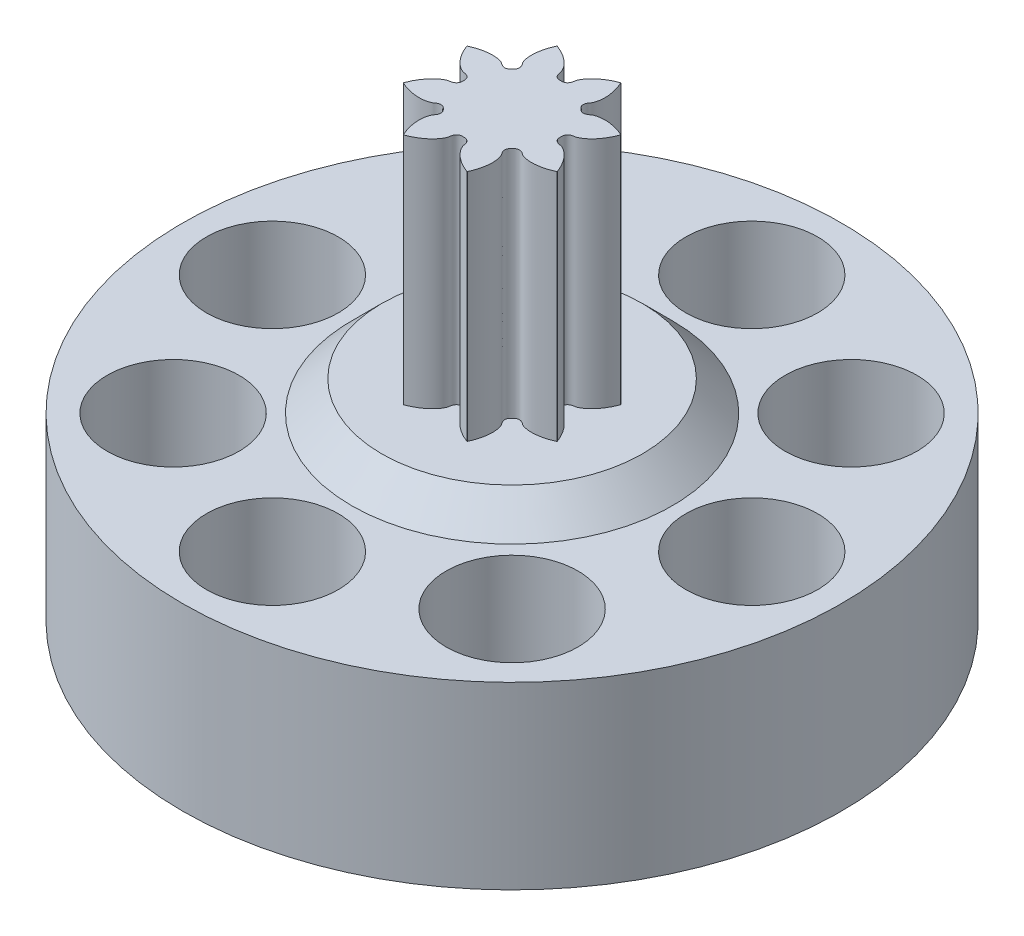
SolidWorks part; units mm, degrees
other "Markup1"
sketch "Sketch16" plane through (11, -3, 11) normal (0.0109, -0.9996, 0.0259) x (-0.0225, -0.0261, -0.9994)
ref_plane "Front Plane" through (0, 0, 0) normal (0, 0, 1) x (1, 0, 0)
ref_plane "Top Plane" through (0, 0, 0) normal (0, 1, 0) x (1, 0, 0)
ref_plane "Right Plane" through (0, 0, 0) normal (1, 0, 0) x (0, 0, -1)
sketch "Sketch1" plane through (0, 0, 0) normal (0, 1, 0) x (1, 0, 0)
  circle A0 centre (0, 0) radius 11
  dimension "D1" = 22
extrude "Boss-Extrude1" add sketch "Sketch1" along normal mid plane 6
sketch "Sketch2" plane through (0, 3, 0) normal (0, 1, 0) x (1, 0, 0)
  circle A0 centre (0, 8) radius 1
  circle A1 centre (-5.6569, 5.6569) radius 1
  circle A2 centre (5.6569, 5.6569) radius 1
  circle A3 centre (-5.6569, -5.6569) radius 1
  circle A4 centre (5.6569, -5.6569) radius 1
  circle A5 centre (-8, 0) radius 1
  circle A6 centre (0, -8) radius 1
  circle A7 centre (8, 0) radius 1
  circle A8 centre (0, 0) radius 4
  circle A9 centre (0, 0) radius 11
sketch "Sketch5" plane through (0, 3, 0) normal (0, 1, 0) x (1, 0, 0)
  line L0 (2.5656, 1.0576) -> (2.562, 1.0663)
  line L1 (1.0663, 2.562) -> (1.0576, 2.5656)
  line L2 (-1.0576, 2.5656) -> (-1.0663, 2.562)
  line L3 (-2.562, 1.0663) -> (-2.5656, 1.0576)
  line L4 (-2.5656, -1.0576) -> (-2.562, -1.0663)
  line L5 (-1.0663, -2.562) -> (-1.0576, -2.5656)
  line L6 (1.0576, -2.5656) -> (1.0663, -2.562)
  line L7 (2.562, -1.0663) -> (2.5656, -1.0576)
  circle A1 centre (0, 0) radius 2.8
  spline S0 degree 3 poles (2.5656, 1.0576) (2.5467, 1.0063) (2.5127, 0.9243) (2.4586, 0.8162) (2.4108, 0.7326) (2.3616, 0.6567) (2.3117, 0.5883) (2.2618, 0.5274) (2.2125, 0.4736) (2.1645, 0.4267) (2.1184, 0.3865) (2.0746, 0.3524) (2.0339, 0.3241) (1.9966, 0.3012) (1.9632, 0.2831) (1.9342, 0.2695) (1.9099, 0.2596) (1.8905, 0.253) (1.8694, 0.2467) (1.8487, 0.2452) (1.828, 0.2423) (1.8074, 0.2387) (1.7821, 0.2325) (1.7521, 0.2221) (1.7278, 0.2103) (1.7086, 0.1983) (1.6939, 0.1875) (1.6793, 0.1746) (1.665, 0.1592) (1.6515, 0.1408) (1.6395, 0.1191) (1.6301, 0.0941) (1.6246, 0.0677) (1.6231, 0.036) (1.6249, 0) (1.6231, -0.036) (1.6246, -0.0677) (1.6301, -0.0941) (1.6395, -0.1191) (1.6515, -0.1408) (1.665, -0.1592) (1.6793, -0.1746) (1.6982, -0.1913) (1.7224, -0.2076) (1.7521, -0.2221) (1.7821, -0.2325) (1.8074, -0.2387) (1.828, -0.2423) (1.8487, -0.2452) (1.8694, -0.2467) (1.8905, -0.253) (1.9099, -0.2596) (1.9342, -0.2695) (1.9632, -0.2831) (1.9966, -0.3012) (2.0339, -0.3241) (2.0746, -0.3524) (2.1184, -0.3865) (2.1645, -0.4267) (2.2125, -0.4736) (2.2618, -0.5274) (2.3117, -0.5883) (2.3616, -0.6567) (2.4108, -0.7326) (2.4586, -0.8162) (2.5127, -0.9243) (2.5467, -1.0063) (2.5656, -1.0576) knots 0.018496 0.018496 0.018496 0.018496 0.071158 0.103928 0.134826 0.16385 0.191003 0.216283 0.23969 0.261224 0.280886 0.298676 0.314593 0.328637 0.340809 0.351108 0.359535 0.366089 0.37077 0.380767 0.385886 0.390938 0.400931 0.410975 0.421412 0.426928 0.432746 0.438959 0.445665 0.452957 0.460893 0.469469 0.478579 0.486756 0.5 0.513244 0.521421 0.530531 0.539107 0.547043 0.554335 0.561041 0.567254 0.578588 0.589025 0.599069 0.609062 0.614114 0.619233 0.62923 0.633911 0.640465 0.648892 0.659191 0.671363 0.685407 0.701324 0.719114 0.738776 0.76031 0.783717 0.808997 0.83615 0.865174 0.896072 0.928842 0.981504 0.981504 0.981504 0.981504
  spline S1 degree 3 poles (1.0663, 2.562) (1.0892, 2.5123) (1.1232, 2.4303) (1.1614, 2.3156) (1.1867, 2.2227) (1.2056, 2.1343) (1.2186, 2.0507) (1.2264, 1.9723) (1.2296, 1.8994) (1.2288, 1.8323) (1.2246, 1.7712) (1.2178, 1.7162) (1.209, 1.6673) (1.1988, 1.6248) (1.188, 1.5884) (1.1771, 1.5582) (1.1669, 1.534) (1.1579, 1.5157) (1.1474, 1.4963) (1.1339, 1.4806) (1.1212, 1.464) (1.1092, 1.4468) (1.0957, 1.4245) (1.0819, 1.396) (1.0731, 1.3704) (1.0679, 1.3484) (1.0652, 1.3304) (1.0639, 1.3109) (1.0647, 1.2899) (1.0682, 1.2673) (1.0751, 1.2435) (1.0861, 1.2192) (1.1009, 1.1966) (1.1223, 1.1732) (1.149, 1.149) (1.1732, 1.1223) (1.1966, 1.1009) (1.2192, 1.0861) (1.2435, 1.0751) (1.2673, 1.0682) (1.2899, 1.0647) (1.3109, 1.0639) (1.3361, 1.0655) (1.3647, 1.0711) (1.396, 1.0819) (1.4245, 1.0957) (1.4468, 1.1092) (1.464, 1.1212) (1.4806, 1.1339) (1.4963, 1.1474) (1.5157, 1.1579) (1.534, 1.1669) (1.5582, 1.1771) (1.5884, 1.188) (1.6248, 1.1988) (1.6673, 1.209) (1.7162, 1.2178) (1.7712, 1.2246) (1.8323, 1.2288) (1.8994, 1.2296) (1.9723, 1.2264) (2.0507, 1.2186) (2.1343, 1.2056) (2.2227, 1.1867) (2.3156, 1.1614) (2.4303, 1.1232) (2.5123, 1.0892) (2.562, 1.0663) knots 0.018496 0.018496 0.018496 0.018496 0.071158 0.103928 0.134826 0.16385 0.191003 0.216283 0.23969 0.261224 0.280886 0.298676 0.314593 0.328637 0.340809 0.351108 0.359535 0.366089 0.37077 0.380767 0.385886 0.390938 0.400931 0.410975 0.421412 0.426928 0.432746 0.438959 0.445665 0.452957 0.460893 0.469469 0.478579 0.486756 0.5 0.513244 0.521421 0.530531 0.539107 0.547043 0.554335 0.561041 0.567254 0.578588 0.589025 0.599069 0.609062 0.614114 0.619233 0.62923 0.633911 0.640465 0.648892 0.659191 0.671363 0.685407 0.701324 0.719114 0.738776 0.76031 0.783717 0.808997 0.83615 0.865174 0.896072 0.928842 0.981504 0.981504 0.981504 0.981504
  spline S2 degree 3 poles (-1.0576, 2.5656) (-1.0063, 2.5467) (-0.9243, 2.5127) (-0.8162, 2.4586) (-0.7326, 2.4108) (-0.6567, 2.3616) (-0.5883, 2.3117) (-0.5274, 2.2618) (-0.4736, 2.2125) (-0.4267, 2.1645) (-0.3865, 2.1184) (-0.3524, 2.0746) (-0.3241, 2.0339) (-0.3012, 1.9966) (-0.2831, 1.9632) (-0.2695, 1.9342) (-0.2596, 1.9099) (-0.253, 1.8905) (-0.2467, 1.8694) (-0.2452, 1.8487) (-0.2423, 1.828) (-0.2387, 1.8074) (-0.2325, 1.7821) (-0.2221, 1.7521) (-0.2103, 1.7278) (-0.1983, 1.7086) (-0.1875, 1.6939) (-0.1746, 1.6793) (-0.1592, 1.665) (-0.1408, 1.6515) (-0.1191, 1.6395) (-0.0941, 1.6301) (-0.0677, 1.6246) (-0.036, 1.6231) (0, 1.6249) (0.036, 1.6231) (0.0677, 1.6246) (0.0941, 1.6301) (0.1191, 1.6395) (0.1408, 1.6515) (0.1592, 1.665) (0.1746, 1.6793) (0.1913, 1.6982) (0.2076, 1.7224) (0.2221, 1.7521) (0.2325, 1.7821) (0.2387, 1.8074) (0.2423, 1.828) (0.2452, 1.8487) (0.2467, 1.8694) (0.253, 1.8905) (0.2596, 1.9099) (0.2695, 1.9342) (0.2831, 1.9632) (0.3012, 1.9966) (0.3241, 2.0339) (0.3524, 2.0746) (0.3865, 2.1184) (0.4267, 2.1645) (0.4736, 2.2125) (0.5274, 2.2618) (0.5883, 2.3117) (0.6567, 2.3616) (0.7326, 2.4108) (0.8162, 2.4586) (0.9243, 2.5127) (1.0063, 2.5467) (1.0576, 2.5656) knots 0.018496 0.018496 0.018496 0.018496 0.071158 0.103928 0.134826 0.16385 0.191003 0.216283 0.23969 0.261224 0.280886 0.298676 0.314593 0.328637 0.340809 0.351108 0.359535 0.366089 0.37077 0.380767 0.385886 0.390938 0.400931 0.410975 0.421412 0.426928 0.432746 0.438959 0.445665 0.452957 0.460893 0.469469 0.478579 0.486756 0.5 0.513244 0.521421 0.530531 0.539107 0.547043 0.554335 0.561041 0.567254 0.578588 0.589025 0.599069 0.609062 0.614114 0.619233 0.62923 0.633911 0.640465 0.648892 0.659191 0.671363 0.685407 0.701324 0.719114 0.738776 0.76031 0.783717 0.808997 0.83615 0.865174 0.896072 0.928842 0.981504 0.981504 0.981504 0.981504
  spline S3 degree 3 poles (-2.562, 1.0663) (-2.5123, 1.0892) (-2.4303, 1.1232) (-2.3156, 1.1614) (-2.2227, 1.1867) (-2.1343, 1.2056) (-2.0507, 1.2186) (-1.9723, 1.2264) (-1.8994, 1.2296) (-1.8323, 1.2288) (-1.7712, 1.2246) (-1.7162, 1.2178) (-1.6673, 1.209) (-1.6248, 1.1988) (-1.5884, 1.188) (-1.5582, 1.1771) (-1.534, 1.1669) (-1.5157, 1.1579) (-1.4963, 1.1474) (-1.4806, 1.1339) (-1.464, 1.1212) (-1.4468, 1.1092) (-1.4245, 1.0957) (-1.396, 1.0819) (-1.3704, 1.0731) (-1.3484, 1.0679) (-1.3304, 1.0652) (-1.3109, 1.0639) (-1.2899, 1.0647) (-1.2673, 1.0682) (-1.2435, 1.0751) (-1.2192, 1.0861) (-1.1966, 1.1009) (-1.1732, 1.1223) (-1.149, 1.149) (-1.1223, 1.1732) (-1.1009, 1.1966) (-1.0861, 1.2192) (-1.0751, 1.2435) (-1.0682, 1.2673) (-1.0647, 1.2899) (-1.0639, 1.3109) (-1.0655, 1.3361) (-1.0711, 1.3647) (-1.0819, 1.396) (-1.0957, 1.4245) (-1.1092, 1.4468) (-1.1212, 1.464) (-1.1339, 1.4806) (-1.1474, 1.4963) (-1.1579, 1.5157) (-1.1669, 1.534) (-1.1771, 1.5582) (-1.188, 1.5884) (-1.1988, 1.6248) (-1.209, 1.6673) (-1.2178, 1.7162) (-1.2246, 1.7712) (-1.2288, 1.8323) (-1.2296, 1.8994) (-1.2264, 1.9723) (-1.2186, 2.0507) (-1.2056, 2.1343) (-1.1867, 2.2227) (-1.1614, 2.3156) (-1.1232, 2.4303) (-1.0892, 2.5123) (-1.0663, 2.562) knots 0.018496 0.018496 0.018496 0.018496 0.071158 0.103928 0.134826 0.16385 0.191003 0.216283 0.23969 0.261224 0.280886 0.298676 0.314593 0.328637 0.340809 0.351108 0.359535 0.366089 0.37077 0.380767 0.385886 0.390938 0.400931 0.410975 0.421412 0.426928 0.432746 0.438959 0.445665 0.452957 0.460893 0.469469 0.478579 0.486756 0.5 0.513244 0.521421 0.530531 0.539107 0.547043 0.554335 0.561041 0.567254 0.578588 0.589025 0.599069 0.609062 0.614114 0.619233 0.62923 0.633911 0.640465 0.648892 0.659191 0.671363 0.685407 0.701324 0.719114 0.738776 0.76031 0.783717 0.808997 0.83615 0.865174 0.896072 0.928842 0.981504 0.981504 0.981504 0.981504
  spline S4 degree 3 poles (-2.5656, -1.0576) (-2.5467, -1.0063) (-2.5127, -0.9243) (-2.4586, -0.8162) (-2.4108, -0.7326) (-2.3616, -0.6567) (-2.3117, -0.5883) (-2.2618, -0.5274) (-2.2125, -0.4736) (-2.1645, -0.4267) (-2.1184, -0.3865) (-2.0746, -0.3524) (-2.0339, -0.3241) (-1.9966, -0.3012) (-1.9632, -0.2831) (-1.9342, -0.2695) (-1.9099, -0.2596) (-1.8905, -0.253) (-1.8694, -0.2467) (-1.8487, -0.2452) (-1.828, -0.2423) (-1.8074, -0.2387) (-1.7821, -0.2325) (-1.7521, -0.2221) (-1.7278, -0.2103) (-1.7086, -0.1983) (-1.6939, -0.1875) (-1.6793, -0.1746) (-1.665, -0.1592) (-1.6515, -0.1408) (-1.6395, -0.1191) (-1.6301, -0.0941) (-1.6246, -0.0677) (-1.6231, -0.036) (-1.6249, 0) (-1.6231, 0.036) (-1.6246, 0.0677) (-1.6301, 0.0941) (-1.6395, 0.1191) (-1.6515, 0.1408) (-1.665, 0.1592) (-1.6793, 0.1746) (-1.6982, 0.1913) (-1.7224, 0.2076) (-1.7521, 0.2221) (-1.7821, 0.2325) (-1.8074, 0.2387) (-1.828, 0.2423) (-1.8487, 0.2452) (-1.8694, 0.2467) (-1.8905, 0.253) (-1.9099, 0.2596) (-1.9342, 0.2695) (-1.9632, 0.2831) (-1.9966, 0.3012) (-2.0339, 0.3241) (-2.0746, 0.3524) (-2.1184, 0.3865) (-2.1645, 0.4267) (-2.2125, 0.4736) (-2.2618, 0.5274) (-2.3117, 0.5883) (-2.3616, 0.6567) (-2.4108, 0.7326) (-2.4586, 0.8162) (-2.5127, 0.9243) (-2.5467, 1.0063) (-2.5656, 1.0576) knots 0.018496 0.018496 0.018496 0.018496 0.071158 0.103928 0.134826 0.16385 0.191003 0.216283 0.23969 0.261224 0.280886 0.298676 0.314593 0.328637 0.340809 0.351108 0.359535 0.366089 0.37077 0.380767 0.385886 0.390938 0.400931 0.410975 0.421412 0.426928 0.432746 0.438959 0.445665 0.452957 0.460893 0.469469 0.478579 0.486756 0.5 0.513244 0.521421 0.530531 0.539107 0.547043 0.554335 0.561041 0.567254 0.578588 0.589025 0.599069 0.609062 0.614114 0.619233 0.62923 0.633911 0.640465 0.648892 0.659191 0.671363 0.685407 0.701324 0.719114 0.738776 0.76031 0.783717 0.808997 0.83615 0.865174 0.896072 0.928842 0.981504 0.981504 0.981504 0.981504
  spline S5 degree 3 poles (-1.0663, -2.562) (-1.0892, -2.5123) (-1.1232, -2.4303) (-1.1614, -2.3156) (-1.1867, -2.2227) (-1.2056, -2.1343) (-1.2186, -2.0507) (-1.2264, -1.9723) (-1.2296, -1.8994) (-1.2288, -1.8323) (-1.2246, -1.7712) (-1.2178, -1.7162) (-1.209, -1.6673) (-1.1988, -1.6248) (-1.188, -1.5884) (-1.1771, -1.5582) (-1.1669, -1.534) (-1.1579, -1.5157) (-1.1474, -1.4963) (-1.1339, -1.4806) (-1.1212, -1.464) (-1.1092, -1.4468) (-1.0957, -1.4245) (-1.0819, -1.396) (-1.0731, -1.3704) (-1.0679, -1.3484) (-1.0652, -1.3304) (-1.0639, -1.3109) (-1.0647, -1.2899) (-1.0682, -1.2673) (-1.0751, -1.2435) (-1.0861, -1.2192) (-1.1009, -1.1966) (-1.1223, -1.1732) (-1.149, -1.149) (-1.1732, -1.1223) (-1.1966, -1.1009) (-1.2192, -1.0861) (-1.2435, -1.0751) (-1.2673, -1.0682) (-1.2899, -1.0647) (-1.3109, -1.0639) (-1.3361, -1.0655) (-1.3647, -1.0711) (-1.396, -1.0819) (-1.4245, -1.0957) (-1.4468, -1.1092) (-1.464, -1.1212) (-1.4806, -1.1339) (-1.4963, -1.1474) (-1.5157, -1.1579) (-1.534, -1.1669) (-1.5582, -1.1771) (-1.5884, -1.188) (-1.6248, -1.1988) (-1.6673, -1.209) (-1.7162, -1.2178) (-1.7712, -1.2246) (-1.8323, -1.2288) (-1.8994, -1.2296) (-1.9723, -1.2264) (-2.0507, -1.2186) (-2.1343, -1.2056) (-2.2227, -1.1867) (-2.3156, -1.1614) (-2.4303, -1.1232) (-2.5123, -1.0892) (-2.562, -1.0663) knots 0.018496 0.018496 0.018496 0.018496 0.071158 0.103928 0.134826 0.16385 0.191003 0.216283 0.23969 0.261224 0.280886 0.298676 0.314593 0.328637 0.340809 0.351108 0.359535 0.366089 0.37077 0.380767 0.385886 0.390938 0.400931 0.410975 0.421412 0.426928 0.432746 0.438959 0.445665 0.452957 0.460893 0.469469 0.478579 0.486756 0.5 0.513244 0.521421 0.530531 0.539107 0.547043 0.554335 0.561041 0.567254 0.578588 0.589025 0.599069 0.609062 0.614114 0.619233 0.62923 0.633911 0.640465 0.648892 0.659191 0.671363 0.685407 0.701324 0.719114 0.738776 0.76031 0.783717 0.808997 0.83615 0.865174 0.896072 0.928842 0.981504 0.981504 0.981504 0.981504
  spline S6 degree 3 poles (1.0576, -2.5656) (1.0063, -2.5467) (0.9243, -2.5127) (0.8162, -2.4586) (0.7326, -2.4108) (0.6567, -2.3616) (0.5883, -2.3117) (0.5274, -2.2618) (0.4736, -2.2125) (0.4267, -2.1645) (0.3865, -2.1184) (0.3524, -2.0746) (0.3241, -2.0339) (0.3012, -1.9966) (0.2831, -1.9632) (0.2695, -1.9342) (0.2596, -1.9099) (0.253, -1.8905) (0.2467, -1.8694) (0.2452, -1.8487) (0.2423, -1.828) (0.2387, -1.8074) (0.2325, -1.7821) (0.2221, -1.7521) (0.2103, -1.7278) (0.1983, -1.7086) (0.1875, -1.6939) (0.1746, -1.6793) (0.1592, -1.665) (0.1408, -1.6515) (0.1191, -1.6395) (0.0941, -1.6301) (0.0677, -1.6246) (0.036, -1.6231) (0, -1.6249) (-0.036, -1.6231) (-0.0677, -1.6246) (-0.0941, -1.6301) (-0.1191, -1.6395) (-0.1408, -1.6515) (-0.1592, -1.665) (-0.1746, -1.6793) (-0.1913, -1.6982) (-0.2076, -1.7224) (-0.2221, -1.7521) (-0.2325, -1.7821) (-0.2387, -1.8074) (-0.2423, -1.828) (-0.2452, -1.8487) (-0.2467, -1.8694) (-0.253, -1.8905) (-0.2596, -1.9099) (-0.2695, -1.9342) (-0.2831, -1.9632) (-0.3012, -1.9966) (-0.3241, -2.0339) (-0.3524, -2.0746) (-0.3865, -2.1184) (-0.4267, -2.1645) (-0.4736, -2.2125) (-0.5274, -2.2618) (-0.5883, -2.3117) (-0.6567, -2.3616) (-0.7326, -2.4108) (-0.8162, -2.4586) (-0.9243, -2.5127) (-1.0063, -2.5467) (-1.0576, -2.5656) knots 0.018496 0.018496 0.018496 0.018496 0.071158 0.103928 0.134826 0.16385 0.191003 0.216283 0.23969 0.261224 0.280886 0.298676 0.314593 0.328637 0.340809 0.351108 0.359535 0.366089 0.37077 0.380767 0.385886 0.390938 0.400931 0.410975 0.421412 0.426928 0.432746 0.438959 0.445665 0.452957 0.460893 0.469469 0.478579 0.486756 0.5 0.513244 0.521421 0.530531 0.539107 0.547043 0.554335 0.561041 0.567254 0.578588 0.589025 0.599069 0.609062 0.614114 0.619233 0.62923 0.633911 0.640465 0.648892 0.659191 0.671363 0.685407 0.701324 0.719114 0.738776 0.76031 0.783717 0.808997 0.83615 0.865174 0.896072 0.928842 0.981504 0.981504 0.981504 0.981504
  spline S7 degree 3 poles (2.562, -1.0663) (2.5123, -1.0892) (2.4303, -1.1232) (2.3156, -1.1614) (2.2227, -1.1867) (2.1343, -1.2056) (2.0507, -1.2186) (1.9723, -1.2264) (1.8994, -1.2296) (1.8323, -1.2288) (1.7712, -1.2246) (1.7162, -1.2178) (1.6673, -1.209) (1.6248, -1.1988) (1.5884, -1.188) (1.5582, -1.1771) (1.534, -1.1669) (1.5157, -1.1579) (1.4963, -1.1474) (1.4806, -1.1339) (1.464, -1.1212) (1.4468, -1.1092) (1.4245, -1.0957) (1.396, -1.0819) (1.3704, -1.0731) (1.3484, -1.0679) (1.3304, -1.0652) (1.3109, -1.0639) (1.2899, -1.0647) (1.2673, -1.0682) (1.2435, -1.0751) (1.2192, -1.0861) (1.1966, -1.1009) (1.1732, -1.1223) (1.149, -1.149) (1.1223, -1.1732) (1.1009, -1.1966) (1.0861, -1.2192) (1.0751, -1.2435) (1.0682, -1.2673) (1.0647, -1.2899) (1.0639, -1.3109) (1.0655, -1.3361) (1.0711, -1.3647) (1.0819, -1.396) (1.0957, -1.4245) (1.1092, -1.4468) (1.1212, -1.464) (1.1339, -1.4806) (1.1474, -1.4963) (1.1579, -1.5157) (1.1669, -1.534) (1.1771, -1.5582) (1.188, -1.5884) (1.1988, -1.6248) (1.209, -1.6673) (1.2178, -1.7162) (1.2246, -1.7712) (1.2288, -1.8323) (1.2296, -1.8994) (1.2264, -1.9723) (1.2186, -2.0507) (1.2056, -2.1343) (1.1867, -2.2227) (1.1614, -2.3156) (1.1232, -2.4303) (1.0892, -2.5123) (1.0663, -2.562) knots 0.018496 0.018496 0.018496 0.018496 0.071158 0.103928 0.134826 0.16385 0.191003 0.216283 0.23969 0.261224 0.280886 0.298676 0.314593 0.328637 0.340809 0.351108 0.359535 0.366089 0.37077 0.380767 0.385886 0.390938 0.400931 0.410975 0.421412 0.426928 0.432746 0.438959 0.445665 0.452957 0.460893 0.469469 0.478579 0.486756 0.5 0.513244 0.521421 0.530531 0.539107 0.547043 0.554335 0.561041 0.567254 0.578588 0.589025 0.599069 0.609062 0.614114 0.619233 0.62923 0.633911 0.640465 0.648892 0.659191 0.671363 0.685407 0.701324 0.719114 0.738776 0.76031 0.783717 0.808997 0.83615 0.865174 0.896072 0.928842 0.981504 0.981504 0.981504 0.981504
  dimension "D2" = 5.6
extrude "Boss-Extrude2" add sketch "Sketch5" along normal blind 8.8 contours S7 L7 S0 L0 S1 L1 S2 L2 S3 L3 S4 L4 S5 L5 S6 L6 region at (0, 3, 0)
hole_wizard "CBORE for M2 SHCS3" positions "Sketch11" profile "Sketch13" counterbore size "M2" standard "ANSI Metric"
sketch "Sketch11" plane through (0, 3, 0) normal (0, 1, 0) x (1, 0, 0)
  point P0 (-8, 0)
  point P3 (-5.6569, 5.6569)
  point P6 (0, 8)
  point P9 (5.6569, 5.6569)
  point P12 (8, 0)
  point P15 (5.6569, -5.6569)
  point P18 (0, -8)
  point P21 (-5.6569, -5.6569)
sketch "Sketch13" plane through (-8, 3, 0) normal (1, 0, 0) x (0, 0, 1)
  line L0 (0, 0) -> (0, 6.7811)
  line L1 (0, 6.7811) -> (1.3, 6)
  line L2 (1.3, 6) -> (1.3, 5)
  line L3 (1.3, 5) -> (2.2, 5)
  line L4 (2.2, 5) -> (2.2, 0)
  line L5 (2.2, 0) -> (0, 0)
  line L10 (0, 6.7811) -> (-1.3, 6) construction
  line L11 (0, -6.35) -> (0, 107.95) construction
  dimension "Hole Dia." = 2.6
  dimension "Hole Depth" = 6
  dimension "C'Bore Dia." = 4.4
  dimension "C'Bore Depth" = 5
  dimension "Drill Angle" = 118
sketch "Sketch14" plane through (0, -3, 0) normal (0, -1, 0) x (1, 0, 0)
  circle A0 centre (0, 0) radius 4.2
  dimension "D1" = 8.4
extrude "Cut-Extrude4" cut sketch "Sketch14" against normal blind 5.95
sketch "Sketch15" plane through (0, 3, 0) normal (0, 1, 0) x (1, 0, 0)
  circle A0 centre (0, 0) radius 4.35
  dimension "D1" = 8.7
extrude "Boss-Extrude4" add sketch "Sketch15" along normal blind 1
chamfer "Chamfer1" distance 1 angle 45 1 edges at (0, 3, 4.35)
